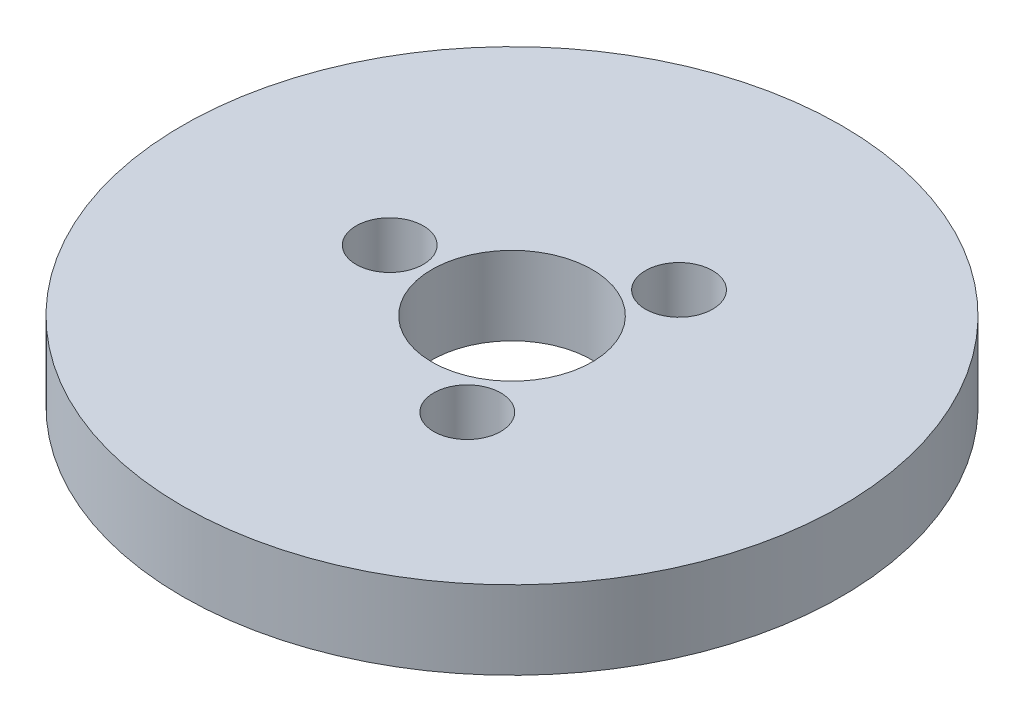
SolidWorks part; units mm, degrees
ref_plane "Front Plane" through (0, 0, 0) normal (0, 0, 1) x (1, 0, 0)
ref_plane "Top Plane" through (0, 0, 0) normal (0, 1, 0) x (1, 0, 0)
ref_plane "Right Plane" through (0, 0, 0) normal (1, 0, 0) x (0, 0, -1)
sketch "Sketch1" plane through (0, 0, 0) normal (0, 1, 0) x (1, 0, 0)
  circle A0 centre (0, 0) radius 92.5
  dimension "FLANGE_OD" = 185
extrude "Boss-Extrude1" add sketch "Sketch1" along normal blind 22
sketch "Sketch2" plane through (0, 0, 0) normal (0, 1, 0) x (1, 0, 0)
  circle A0 centre (0, 0) radius 22.5
  dimension "BORE_D" = 45
extrude "Cut-Extrude1" cut sketch "Sketch2" along normal through all
sketch "Sketch3" plane through (0, 22, 0) normal (0, 1, 0) x (1, 0, 0)
  circle A0 centre (0, 0) radius 34.3237 construction
  circle A1 centre (-34.3237, 0) radius 9.4145
  dimension "BOLT_D" = 18.829
  dimension "BOLT_PCD" = 68.6474
extrude "Cut-Extrude2" cut sketch "Sketch3" against normal blind 18.9956
pattern_circular "CirPattern1" count 3 over 360 about axis through (0, 0, 0) along (0, 1, 0) of "Cut-Extrude2"
